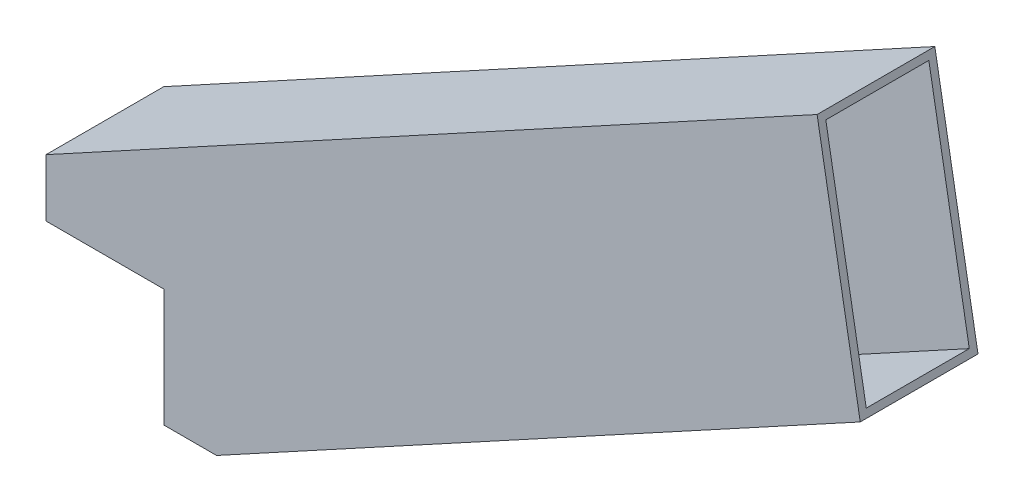
SolidWorks part; units mm, degrees
material "6061-T6 (SS)"
ref_plane "Front" through (0, 0, 0) normal (0, 0, 1) x (1, 0, 0)
ref_plane "Top" through (0, 0, 0) normal (0, 1, 0) x (1, 0, 0)
ref_plane "Right" through (0, 0, 0) normal (1, 0, 0) x (0, 0, -1)
sketch "Sketch1" plane through (0, 0, 0) normal (0, 0, 1) x (1, 0, 0)
  line L0 (184.6516, -98.3142) -> (144.1044, 131.6406) construction
  line L1 (0, 0) -> (-50.8, 0) construction
  line L2 (0, 0) -> (0, 25.4) construction
  line L3 (0, 25.4) -> (-50.8, 25.4) construction
  line L4 (-50.8, 0) -> (-50.8, 25.4) construction
  line L5 (184.6516, -98.3142) -> (210.0516, -98.3142) construction
  line L6 (144.1044, 131.6406) -> (-22.225, 40.976)
  line L7 (153.4115, 78.857) -> (14.5686, 3.175)
  line L9 (144.1044, 131.6406) -> (153.4115, 78.857)
  line L11 (3.175, 3.175) -> (3.175, 28.575)
  line L12 (3.175, 28.575) -> (-22.225, 28.575) construction
  line L15 (-22.225, 28.575) -> (3.175, 28.575)
  line L16 (-50.8, 25.4) -> (-44.9753, 28.575) construction
  line L17 (-22.225, 40.976) -> (-22.225, 28.575)
  line L18 (3.175, 3.175) -> (14.5686, 3.175)
  dimension "D1" = 50.8
  dimension "D2" = 25.4
  dimension "D3" = 100
  dimension "D4" = 106.2406
  dimension "D5" = 144.1044
  dimension "D6" = 25.4
  dimension "D7" = 233.5022
  dimension "D8" = 50.8
  dimension "D9" = 71.406
  dimension "D10" = 221.9792
  dimension "D11" = 3.175
  dimension "D12" = 3.175
  dimension "D13" = 25.4
  dimension "D14" = 25.4
extrude "Boss-Extrude1" add sketch "Sketch1" along normal blind 25.4
shell "Shell1" thickness 1.5875 removed face at (-9.525, 28.575, 12.7) removed face at (3.175, 15.875, 12.7) removed face at (148.7579, 105.2488, 12.7) removed face at (8.8718, 3.175, 12.7) removed face at (-22.225, 34.7755, 12.7)
